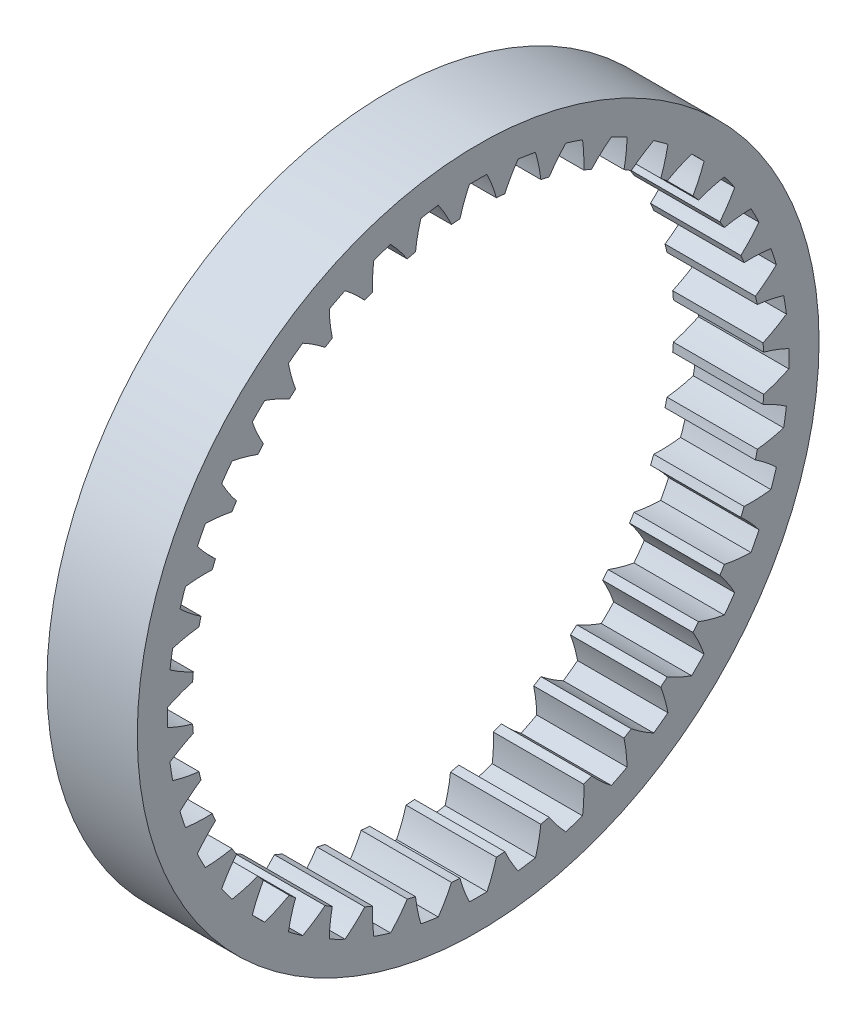
SolidWorks part; units mm, degrees
ref_plane "Plane1" through (0, 0, 0) normal (0, 0, 1) x (1, 0, 0)
ref_plane "Plane2" through (0, 0, 0) normal (0, 1, 0) x (1, 0, 0)
ref_plane "Plane3" through (0, 0, 0) normal (1, 0, 0) x (0, 0, -1)
sketch "HoldingSke" plane through (0, 0, 0) normal (0, 1, 0) x (1, 0, 0)
  line L0 (0, 0) -> (0.383, -0.3214)
  line L1 (-15, 0) -> (100, 0) construction
  line L2 (0, 0) -> (-2.1039, 2.3779)
  line L3 (0, 0) -> (-11.863, 4.5341)
  line L4 (0, 0) -> (6.6156, 5.5511)
  line L5 (0, 0) -> (-23.7986, -8.8762)
  line L6 (0, 0) -> (-10.5278, -7.1032)
  line L7 (-2.1039, 2.3779) -> (3.3635, 27.1825)
  line L8 (-76.2, 4.3779) -> (-54.61, 4.3779)
  line L9 (-71.009, 38.7566) -> (-53.1078, 45.2721)
  line L10 (-76.2, 71.12) -> (104.1128, 71.12)
  line L11 (0, 0) -> (-12, 0)
  line L12 (-76.2, 101.6) -> (-76.133, 101.6)
  line L13 (24.9733, 27.94) -> (52.9518, 28.4284)
  line L14 (24.9733, 27.94) -> (24.9743, 27.94)
  line L15 (24.9733, 27.94) -> (100.4006, 29.5858)
  circle A0 centre (0, 0) radius 12.5
  circle A1 centre (0, 0) radius 12.7
  circle A2 centre (0, 0) radius 12.7
  dimension "MHD" = 25.4
  dimension "Hub_dia" = 25.4
  dimension "Diameter" = 25
  dimension "Num_teeth" = 40
  dimension "Pitch" = 0.5
  dimension "Overall_len" = 25.4
  dimension "Show_teeth" = 40
  dimension "Thickness" = 12.7
  dimension "OAL" = 25.4001
  dimension "T_dim" = 21.59
  dimension "Ap" = 20
  dimension "H" = 19.05
  dimension "Pitch_radius" = 180.3128
  dimension "Width" = 12
  dimension "Backlash" = 0.067
  dimension "Addendum_fac" = 1
  dimension "Dedendum_fac" = 1.25
  dimension "Clearance_fac" = 0.25
  dimension "Dedendum_add" = 0.001
  dimension "Module" = 2
sketch "BasProSke" plane through (0, 0, 0) normal (0, 1, 0) x (1, 0, 0)
  line L0 (-10, 0) -> (60, 0) construction
  line L1 (0, 38) -> (0, 42.5264)
  line L2 (0, 38) -> (12, 38)
  line L3 (12, 38) -> (12, 42.5264)
  line L4 (12, 42.5264) -> (0, 42.5264)
  dimension "Thickness" = 12
  dimension "Diameter" = 85.0528
  dimension "Inside_diameter" = 76
revolve "Base-Revolve" add sketch "BasProSke" angle 360 about L0
sketch "TooCutSke" plane through (0, 0, 0) normal (1, 0, 0) x (0, 0, -1)
  line L3 (1.7379, 39.9622) -> (1.7379, 53.6633) construction
  line L4 (0, 0) -> (0, 59.563) construction
  line L5 (0, 0) -> (-5.3609, 68.1169) construction
  line L6 (-16.8604, 32.6066) -> (35.072, 36.6938) construction
  circle A0 centre (0, 0) radius 40 construction
  circle A1 centre (0, 0) radius 42.501 construction
  circle A2 centre (0, 0) radius 33.8289 construction
  circle A3 centre (0, 0) radius 37.9746 construction
  arc A4 (2.4273, 37.8969) -> (0.5225, 42.4978) centre (-16.8604, 32.6066) ccw
  arc A5 (2.4273, 37.8969) -> (-2.4273, 37.8969) centre (0, 0) ccw
  arc A6 (0.5225, 42.4978) -> (-0.5225, 42.4978) centre (0, 0) ccw
  arc A7 (-0.5225, 42.4978) -> (-2.4273, 37.8969) centre (16.8604, 32.6066) ccw
  dimension "Pitch_dia" = 80
  dimension "Base_dia" = 67.6579
  dimension "Root_dia" = 85.002
  dimension "Overcut_dia" = 75.9492
  dimension "Flank_rad" = 20
  dimension "Half_ang" = 4.5
  dimension "Half_CT" = 1.7379
extrude "ToothCut" cut sketch "TooCutSke" along normal through all
fillet "Breaks" [suppressed] radius 0.2
fillet "RootFillets" [suppressed] radius 0.501
pattern_circular "TeethCuts" count 40 every 9 about axis through (-10, 0, 0) along (1, 0, 0) of "RootFillets", "Breaks", "ToothCut"
sketch "Sketch1" plane through (0, 0, 0) normal (1, 0, 0) x (0, 0, -1)
  circle A0 centre (0, 0) radius 41.2764
extrude "Extrude-Thin1" add sketch "Sketch1" along normal through all thin thin type one direction wall 4
scale "Scale1" scale about origin uniform scaling yes scale factor 0.4
equation "' \"Module@HoldingSke\" = 6.35"
equation "' \"Num_teeth@HoldingSke\" = 24"
equation "' \"Ap@HoldingSke\" =  14.5"
equation "' \"Ap@HoldingSke\" = 14.5"
equation "' \"Width@HoldingSke\" = 12"
equation "' \"Diameter@HoldingSke\" = 8 * 25.4"
equation "' \"Show_teeth@HoldingSke\" = 100"
equation "' \"Backlash@HoldingSke\" = 0.009 * 25.4"
equation "' \"Addendum_fac@HoldingSke\" = 1.0"
equation "' \"Dedendum_fac@HoldingSke\" = 1.25"
equation "' \"Dedendum_add@HoldingSke\" = 0.00005 * 25.4"
equation "' \"Clearance_fac@HoldingSke\" = 0.25"
equation "\"Pitch@HoldingSke\" = 1 / \"Module@HoldingSke\" "
equation "\"Overcut_dia@TooCutSke\" = (\"Num_teeth@HoldingSke\" - 2 * \"Addendum_fac@HoldingSke\") / \"Pitch@HoldingSke\" - 0.002 * 25.4"
equation "\"Pitch_dia@TooCutSke\" = \"Num_teeth@HoldingSke\" / \"Pitch@HoldingSke\""
equation "\"Base_dia@TooCutSke\" = \"Num_teeth@HoldingSke\" / \"Pitch@HoldingSke\" * cos((\"Ap@HoldingSke\"  * 3.14159265 / 180)) * 0.90"
equation "\"Root_dia@TooCutSke\" = \"Num_teeth@HoldingSke\"  / \"Pitch@HoldingSke\" + 2 *  \"Dedendum_fac@HoldingSke\"/ \"Pitch@HoldingSke\" + \"Dedendum_add@HoldingSke\" * 2"
equation "\"Half_ang@TooCutSke\" = 180 / \"Num_teeth@HoldingSke\""
equation "\"Half_CT@TooCutSke\" = \"Num_teeth@HoldingSke\" / \"Pitch@HoldingSke\" * sin((3.14159265 / 2 / \"Num_teeth@HoldingSke\")) / 2 + 10 * \"Backlash@HoldingSke\" / 4"
equation "\"Flank_rad@TooCutSke\" = \"Num_teeth@HoldingSke\" / \"Pitch@HoldingSke\" / 4"
equation "\"Radius@RootFillets\"= \"Clearance_fac@HoldingSke\" / \"Pitch@HoldingSke\" + \"Dedendum_add@HoldingSke\""
equation "\"Break_rad@Breaks\" = 0.02 / \"Pitch@HoldingSke\" * 5"
equation "\"Num_teeth@TeethCuts\" = int( \"Show_teeth@HoldingSke\" ) + 1"
equation "\"Num_teeth@TeethCuts\" = ((sgn( \"Num_teeth@TeethCuts\" - \"Num_teeth@HoldingSke\" )-1)*( \"Num_teeth@TeethCuts\" - \"Num_teeth@HoldingSke\" ))/-2+ \"Num_teeth@HoldingSke\""
equation "\"Num_teeth@TeethCuts\" = ((sgn( \"Num_teeth@TeethCuts\" - 2.0)+1)*( \"Num_teeth@TeethCuts\" - 2.0))/2 +2.0"
equation "\"Angle@TeethCuts\" = 360.0 / \"Num_teeth@HoldingSke\""
equation "\"Diameter@BasProSke\" = \"Num_teeth@HoldingSke\"  / \"Pitch@HoldingSke\" + 2 *  \"Dedendum_fac@HoldingSke\"/ \"Pitch@HoldingSke\" + \"Dedendum_add@HoldingSke\" * 2 + 0.002 * 25.4"
equation "\"Diameter@BasProSke\" = ((sgn( \"Diameter@BasProSke\"  - \"Diameter@HoldingSke\" )+1)*( \"Diameter@BasProSke\"  - \"Diameter@HoldingSke\" ))/2 + \"Diameter@HoldingSke\""
equation "\"Inside_diameter@BasProSke\" =  (\"Num_teeth@HoldingSke\" - 2 * \"Addendum_fac@HoldingSke\") / \"Pitch@HoldingSke\" "
equation "\"Thickness@BasProSke\"  = \"Width@HoldingSke\""
